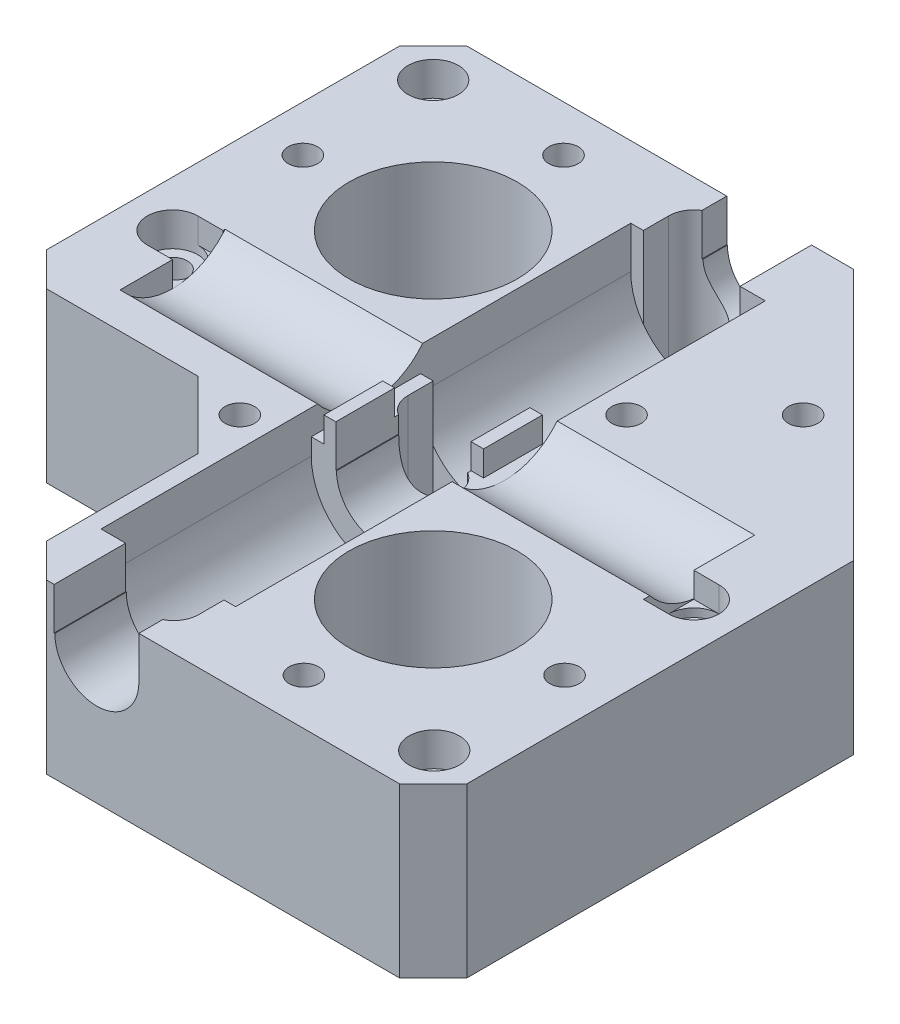
SolidWorks part; units mm, degrees
ref_plane "Front Plane" through (0, 0, 0) normal (0, 0, 1) x (1, 0, 0)
ref_plane "Top Plane" through (0, 0, 0) normal (0, 1, 0) x (1, 0, 0)
ref_plane "Right Plane" through (0, 0, 0) normal (1, 0, 0) x (0, 0, -1)
sketch "Sketch2" plane through (0, 0, 0) normal (0, 1, 0) x (1, 0, 0)
  line L1 (-40, -40) -> (40, -40)
  line L2 (-40, -40) -> (-40, 40)
  line L3 (-40, 40) -> (40, 40)
  line L4 (40, -40) -> (40, 40)
  line L5 (-40, -40) -> (40, 40) construction
  line L6 (-40, 40) -> (40, -40) construction
  point P0 (0, 0)
  dimension "D1" = 80
  dimension "D2" = 80
extrude "Boss-Extrude1" add sketch "Sketch2" along normal blind 20
sketch "Sketch4" plane through (0, 20, 0) normal (0, 1, 0) x (1, 0, 0)
  circle A0 centre (-3.5, 3.5) radius 1.75
  circle A1 centre (3.5, -3.5) radius 1.75
  circle A2 centre (-3.5, 34.5) radius 1.75
  circle A3 centre (-34.5, 34.5) radius 1.75
  circle A4 centre (-34.5, 3.5) radius 1.75
  circle A5 centre (3.6244, -34.5) radius 1.75
  circle A6 centre (34.6244, -34.5) radius 1.75
  circle A7 centre (34.5, -3.5) radius 1.75
  point P0 (3.5, -3.5)
  point P1 (-3.5, 3.5)
  point P2 (-3.5, 34.5)
  point P3 (-34.5, 3.5)
  point P4 (-34.5, 34.5)
  point P5 (34.5, -3.5)
  point P6 (3.6244, -34.5)
  point P7 (34.6244, -34.5)
  dimension "D16" = 3.5
  dimension "D17" = 3.5
  dimension "D18" = 3.5
  dimension "D19" = 3.5
  dimension "D20" = 3.5
  dimension "D21" = 3.5
  dimension "D22" = 3.5
  dimension "D23" = 3.5
  dimension "D1" = 3.5
  dimension "D2" = 3.5
  dimension "D3" = 3.5
  dimension "D4" = 3.5
  dimension "D5" = 31
  dimension "D6" = 31
  dimension "D7" = 0
  dimension "D8" = 0
  dimension "D9" = 31
  dimension "D10" = 31
  dimension "D11" = 31
  dimension "D12" = 31
  dimension "D13" = 31
  dimension "D14" = 31
  dimension "D15" = 0
extrude "Cut-Extrude1" cut sketch "Sketch4" against normal through all both and the other way through all
sketch "Sketch6" plane through (0, 20, 0) normal (0, 1, 0) x (1, 0, 0)
  line L4 (40, -40) -> (40, 40)
  line L5 (40, 40) -> (-40, 40)
  line L6 (-40, 40) -> (-40, -40)
  line L7 (-40, -40) -> (40, -40)
  line L8 (40, -40) -> (40, 40)
  line L9 (40, 40) -> (-40, 40)
  line L10 (-40, 40) -> (-40, -40)
  line L11 (-40, -40) -> (40, -40)
  circle A0 centre (3.6244, -34.5) radius 1.75 construction
  circle A1 centre (34.6244, -34.5) radius 1.75 construction
  circle A2 centre (34.5, -3.5) radius 1.75 construction
  circle A3 centre (3.5, -3.5) radius 1.75 construction
  circle A4 centre (-34.5, 3.5) radius 1.75 construction
  circle A5 centre (-3.5, 3.5) radius 1.75 construction
  circle A6 centre (-3.5, 34.5) radius 1.75 construction
  circle A7 centre (-34.5, 34.5) radius 1.75 construction
  circle A8 centre (3.6244, -34.5) radius 1.75
  circle A9 centre (34.6244, -34.5) radius 1.75
  circle A10 centre (34.5, -3.5) radius 1.75
  circle A11 centre (3.5, -3.5) radius 1.75
  circle A12 centre (-34.5, 3.5) radius 1.75
  circle A13 centre (-3.5, 3.5) radius 1.75
  circle A14 centre (-3.5, 34.5) radius 1.75
  circle A15 centre (-34.5, 34.5) radius 1.75
  circle A16 centre (-3.5, 3.5) radius 3
  circle A17 centre (3.5, -3.5) radius 3
  circle A18 centre (34.5, -3.5) radius 3
  circle A19 centre (34.6244, -34.5) radius 3
  circle A20 centre (3.6244, -34.5) radius 3
  circle A21 centre (-34.5, 3.5) radius 3
  circle A22 centre (-34.5, 34.5) radius 3
  circle A23 centre (-3.5, 34.5) radius 3
  circle M7 centre (-34.5, 34.5) radius 1.75
  dimension "D2" = 6
  dimension "D3" = 6
  dimension "D4" = 6
  dimension "D5" = 6
  dimension "D6" = 6
  dimension "D7" = 6
  dimension "D8" = 6
  dimension "D9" = 6
  dimension "D1" = 0
extrude "Cut-Extrude2" cut sketch "Sketch6" against normal blind 4 contours A22 M7 | M7 | A21 | A23 | A16 | A22 | A17 | A18 | A20 | A19 region at (-34.5, 20, -34.5) region at (-37.4151, 20, -34.5)
chamfer "Chamfer1" distance 4 angle 45 2 edges at (-40, 10, -40) (40, 10, 40)
sketch "Sketch7" plane through (0, 20, 0) normal (0, 1, 0) x (1, 0, 0)
  line L1 (-8, 6.5) -> (8, 6.5)
  line L2 (-8, 6.5) -> (-8, 31.5)
  line L3 (-8, 31.5) -> (8, 31.5)
  line L4 (8, 6.5) -> (8, 31.5)
  line L5 (-8, 6.5) -> (8, 31.5) construction
  line L6 (40, 40) -> (-36, 40)
  line L7 (-36, 40) -> (-40, 36)
  line L8 (-40, 36) -> (-40, -40)
  line L9 (-40, -40) -> (36, -40)
  line L10 (36, -40) -> (40, -36)
  line L11 (40, -36) -> (40, 40)
  line L12 (40, 40) -> (-36, 40)
  line L13 (-36, 40) -> (-40, 36)
  line L14 (-40, 36) -> (-40, -40)
  line L15 (-40, -40) -> (36, -40)
  line L16 (36, -40) -> (40, -36)
  line L17 (40, -36) -> (40, 40)
  line L18 (-8, 31.5) -> (8, 6.5) construction
  line L19 (-6.5, 3.5) -> (-0.5, 3.5)
  line L20 (-6.5, 3.5) -> (-6.5, 6.5)
  line L21 (-6.5, 6.5) -> (-0.5, 6.5)
  line L22 (-0.5, 3.5) -> (-0.5, 6.5)
  line L23 (-6.5, 34.5) -> (-0.5, 34.5)
  line L24 (-6.5, 34.5) -> (-6.5, 31.5)
  line L25 (-6.5, 31.5) -> (-0.5, 31.5)
  line L26 (-0.5, 34.5) -> (-0.5, 31.5)
  circle A0 centre (-3.5, 3.5) radius 3 construction
  circle A1 centre (-3.5, 34.5) radius 3 construction
  circle A2 centre (-3.5, 3.5) radius 3
  circle A3 centre (-3.5, 34.5) radius 3
  point P2 (0, 19)
  circle M12 centre (-3.5, 3.5) radius 3
  circle M13 centre (-3.5, 34.5) radius 3
  dimension "D2" = 16
  dimension "D3" = 0
  dimension "D4" = 25
  dimension "D5" = 19
  dimension "D1" = 0
extrude "Cut-Extrude5" cut sketch "Sketch7" against normal blind 4 contours L24 L3 M13 | L23 M13 | L26 L3 M13 | L1 L4 L3 L2 | L20 L1 M12 | L19 M12 | L22 L1 M12 region at (0, 20, -19) region at (-5.8299, 20, -5.8299) region at (-1.1701, 20, -5.8299) region at (-3.5, 20, -4.7732) region at (-5.8299, 20, -32.1701) region at (-1.1701, 20, -32.1701) region at (-3.5, 20, -33.2268)
sketch "Sketch8" plane through (0, 20, 0) normal (0, 1, 0) x (1, 0, 0)
  line L1 (-8, -31.5) -> (8, -31.5)
  line L2 (-8, -31.5) -> (-8, -6.5)
  line L3 (-8, -6.5) -> (8, -6.5)
  line L4 (8, -31.5) -> (8, -6.5)
  line L5 (-8, -31.5) -> (8, -6.5) construction
  line L6 (40, 40) -> (-36, 40)
  line L7 (-36, 40) -> (-40, 36)
  line L8 (-40, 36) -> (-40, -40)
  line L9 (-40, -40) -> (36, -40)
  line L10 (36, -40) -> (40, -36)
  line L11 (40, -36) -> (40, 40)
  line L12 (40, 40) -> (-36, 40)
  line L13 (-36, 40) -> (-40, 36)
  line L14 (-40, 36) -> (-40, -40)
  line L15 (-40, -40) -> (36, -40)
  line L16 (36, -40) -> (40, -36)
  line L17 (40, -36) -> (40, 40)
  line L18 (-8, -6.5) -> (8, -31.5) construction
  line L19 (6.6244, -34.5) -> (0.6244, -34.5)
  line L20 (6.6244, -34.5) -> (6.6244, -31.5)
  line L21 (6.6244, -31.5) -> (0.6244, -31.5)
  line L22 (0.6244, -34.5) -> (0.6244, -31.5)
  line L23 (0.5, -3.5) -> (6.5, -3.5)
  line L24 (0.5, -3.5) -> (0.5, -6.5)
  line L25 (0.5, -6.5) -> (6.5, -6.5)
  line L26 (6.5, -3.5) -> (6.5, -6.5)
  circle A0 centre (3.6244, -34.5) radius 3 construction
  circle A1 centre (3.5, -3.5) radius 3 construction
  circle A2 centre (3.6244, -34.5) radius 3
  circle A3 centre (3.5, -3.5) radius 3
  point P12 (0, -19)
  dimension "D2" = 25
  dimension "D3" = 19
  dimension "D4" = 16
  dimension "D1" = 0
extrude "Cut-Extrude6" cut sketch "Sketch8" against normal blind 4 contours L22 L23 | L23 L22 | L22 L24 L3 | L26 L22 L3 | L1 L4 L3 L2 | L19 L20 L1 | L19 | L22 L19 L1 | L19 region at (0, 20, 19) region at (1.2945, 20, 32.1701) region at (5.9543, 20, 32.1701) region at (3.6244, 20, 33.2268) region at (3.6244, 20, 35.7732) region at (1.1701, 20, 5.8299) region at (5.8299, 20, 5.8299) region at (3.5, 20, 4.7732) region at (3.5, 20, 2.2268)
sketch "Sketch9" plane through (0, 20, 0) normal (0, 1, 0) x (1, 0, 0)
  line L0 (6.6244, -31.5) -> (8, -31.5) construction
  line L1 (8, -31.5) -> (8, -6.5) construction
  line L2 (-8, -31.5) -> (-8, -6.5) construction
  line L3 (-8, -6.5) -> (0.5, -6.5) construction
  line L4 (-8, 6.5) -> (-6.5, 6.5) construction
  line L5 (-8, 6.5) -> (-8, 31.5) construction
  line L6 (40, 40) -> (-36, 40)
  line L7 (-36, 40) -> (-40, 36)
  line L8 (-40, 36) -> (-40, -40)
  line L9 (-40, -40) -> (36, -40)
  line L10 (36, -40) -> (40, -36)
  line L11 (40, -36) -> (40, 40)
  line L12 (40, 40) -> (-36, 40)
  line L13 (-36, 40) -> (-40, 36)
  line L14 (-40, 36) -> (-40, -40)
  line L15 (-40, -40) -> (36, -40)
  line L16 (36, -40) -> (40, -36)
  line L17 (40, -36) -> (40, 40)
  line L18 (-0.5, 31.5) -> (8, 31.5) construction
  line L19 (8, 6.5) -> (8, 31.5) construction
  line L20 (6.6244, -31.5) -> (8, -31.5)
  line L21 (8, -31.5) -> (8, -6.5)
  line L22 (-8, -31.5) -> (-8, -6.5)
  line L23 (-8, -6.5) -> (0.5, -6.5)
  line L24 (-8, 6.5) -> (-6.5, 6.5)
  line L25 (-8, 6.5) -> (-8, 31.5)
  line L26 (-0.5, 31.5) -> (8, 31.5)
  line L27 (8, 6.5) -> (8, 31.5)
  line L29 (-8, 6.5) -> (8, 6.5)
  line L30 (-8, 6.5) -> (-8, 31.5)
  line L31 (-8, 31.5) -> (8, 31.5)
  line L32 (8, 6.5) -> (8, 31.5)
  line L33 (-8, -31.5) -> (8, -31.5)
  line L34 (-8, -31.5) -> (-8, -6.5)
  line L35 (-8, -6.5) -> (8, -6.5)
  line L36 (8, -31.5) -> (8, -6.5)
  line M8 (-6.5, 6.5) -> (-8, 6.5)
  line M9 (-8, 6.5) -> (-8, 31.5)
  line M10 (-8, 31.5) -> (-6.5, 31.5)
  line M14 (-0.5, 31.5) -> (8, 31.5)
  line M15 (8, 31.5) -> (8, 6.5)
  line M16 (8, 6.5) -> (-0.5, 6.5)
  line M30 (0.6244, -31.5) -> (-8, -31.5)
  line M31 (-8, -31.5) -> (-8, -6.5)
  line M32 (-8, -6.5) -> (0.5, -6.5)
  line M36 (6.5, -6.5) -> (8, -6.5)
  line M37 (8, -6.5) -> (8, -31.5)
  line M38 (8, -31.5) -> (6.6244, -31.5)
  dimension "D1" = 0
extrude "Cut-Extrude7" cut sketch "Sketch9" against normal blind 13 contours L31 L29 M10 M9 M8 M16 M15 M14 | L35 L33 M32 M31 M30 M38 M37 M36 region at (0, 20, 19) region at (0, 20, -19)
fillet "Fillet1" radius 8 4 edges at (8, 7, -19) (-8, 7, -19) (8, 7, 19) (-8, 7, 19)
sketch "Sketch10" plane through (0, 20, 0) normal (0, 1, 0) x (1, 0, 0)
  line L0 (3.5, -0.5) -> (6.5, -0.5)
  line L1 (6.5, -8) -> (31.5, -8)
  line L2 (6.5, -8) -> (6.5, 8)
  line L3 (6.5, 8) -> (31.5, 8)
  line L4 (31.5, -8) -> (31.5, 8)
  line L5 (6.5, -8) -> (31.5, 8) construction
  line L6 (6.5, 8) -> (31.5, -8) construction
  line L8 (-31.5, -8) -> (-6.5, -8)
  line L9 (-31.5, -8) -> (-31.5, 8)
  line L10 (-31.5, 8) -> (-6.5, 8)
  line L11 (-6.5, -8) -> (-6.5, 8)
  line L12 (-31.5, -8) -> (-6.5, 8) construction
  line L13 (-31.5, 8) -> (-6.5, -8) construction
  line L14 (-34.5, 6.5) -> (-31.5, 6.5)
  line L15 (-34.5, 6.5) -> (-34.5, 0.5)
  line L16 (-34.5, 0.5) -> (-31.5, 0.5)
  line L17 (-31.5, 6.5) -> (-31.5, 0.5)
  line L18 (3.5, -0.5) -> (6.5, -0.5)
  line L19 (3.5, -0.5) -> (3.5, -6.5)
  line L20 (3.5, -6.5) -> (6.5, -6.5)
  line L21 (6.5, -0.5) -> (6.5, -6.5)
  line L22 (-3.5, 0.5) -> (-6.5, 0.5)
  line L23 (-3.5, 0.5) -> (-3.5, 6.5)
  line L24 (-3.5, 6.5) -> (-6.5, 6.5)
  line L25 (-6.5, 0.5) -> (-6.5, 6.5)
  line L26 (34.5, -0.5) -> (31.5, -0.5)
  line L27 (34.5, -0.5) -> (34.5, -6.5)
  line L28 (34.5, -6.5) -> (31.5, -6.5)
  line L29 (31.5, -0.5) -> (31.5, -6.5)
  arc A0 (6.5, -3.5) -> (0.5, -3.5) centre (3.5, -3.5) ccw construction
  arc A1 (6.5, -3.5) -> (0.5, -3.5) centre (3.5, -3.5) ccw
  circle A2 centre (-34.5, 3.5) radius 3 construction
  circle A3 centre (34.5, -3.5) radius 3
  circle A4 centre (34.5, -3.5) radius 3
  arc A5 (-6.5, 3.5) -> (-0.5, 3.5) centre (-3.5, 3.5) ccw construction
  circle A6 centre (-34.5, 3.5) radius 3
  arc A7 (-6.5, 3.5) -> (-0.5, 3.5) centre (-3.5, 3.5) ccw
  point P0 (19, 0)
  point P20 (-19, 0)
  line M15 (-6.5, 3.5) -> (-6.5, 6.5)
  line M16 (-6.5, 6.5) -> (-8, 6.5)
  line M17 (-8, 6.5) -> (-8, 31.5)
  line M23 (8, 31.5) -> (8, 6.5)
  line M24 (8, 6.5) -> (-0.5, 6.5)
  arc M26 (-0.5, 3.5) -> (-6.5, 3.5) centre (-3.5, 3.5) cw
  circle M27 centre (-34.5, 3.5) radius 3
  circle M29 centre (34.5, -3.5) radius 3
  line M39 (-8, -31.5) -> (-8, -6.5)
  line M40 (-8, -6.5) -> (0.5, -6.5)
  arc M42 (0.5, -3.5) -> (6.5, -3.5) centre (3.5, -3.5) cw
  line M43 (6.5, -3.5) -> (6.5, -6.5)
  line M44 (6.5, -6.5) -> (8, -6.5)
  line M45 (8, -6.5) -> (8, -31.5)
  dimension "D5" = 0
  dimension "D1" = 16
  dimension "D2" = 25
  dimension "D3" = 19
  dimension "D4" = 0
  dimension "D6" = 25
  dimension "D7" = 19
  dimension "D8" = 16
  dimension "D9" = 0
extrude "Cut-Extrude8" cut sketch "Sketch10" against normal blind 3 contours L27 M29 | L26 L4 M29 | L27 M29 | L28 L4 M29 | L1 L4 L3 L2 M23 M24 M43 M44 M45 | L19 L20 M43 M42 | L2 L0 M42 | L11 L10 L9 L8 M40 M15 M16 M17 M39 | L23 L24 M15 M26 | L22 L11 M26 | L16 L9 M27 | L15 M27 | L14 L9 M27 region at (4.9002, 20, 3.78) region at (5.8299, 20, 1.1701) region at (19.1337, 20, 0) region at (32.1701, 20, 1.1701) region at (32.1701, 20, 5.8299) region at (33.2268, 20, 3.5) region at (35.7732, 20, 3.5) region at (-19.1337, 20, 0) region at (-32.1701, 20, -1.1701) region at (-32.1701, 20, -5.8299) region at (-33.2268, 20, -3.5) region at (-5.8299, 20, -1.1701) region at (-4.9002, 20, -3.78)
sketch "Sketch12" plane through (-31.5, 0, 0) normal (1, 0, 0) x (0, 0, -1)
  line L0 (0.5, 17) -> (8, 17)
  line L1 (8, 20) -> (8, 17)
  line L4 (0.5, 20) -> (-8, 20)
  line L5 (-8, 20) -> (-8, 17)
  line L6 (-8, 17) -> (0.5, 17)
  line L7 (0.5, 17) -> (0.5, 20)
  line L8 (0.5, 20) -> (-8, 20)
  line L9 (-8, 20) -> (-8, 17)
  line L10 (-8, 17) -> (0.5, 17)
  line L11 (0.5, 17) -> (0.5, 20)
  line L12 (8, 20) -> (6.5, 20)
  line L13 (6.5, 20) -> (6.5, 17)
  line L14 (6.5, 17) -> (8, 17)
  line L15 (8, 17) -> (8, 20)
  line L16 (8, 20) -> (6.5, 20)
  line L17 (6.5, 20) -> (6.5, 17)
  line L18 (6.5, 17) -> (8, 17)
  line L19 (8, 17) -> (8, 20)
  circle A0 centre (0.5, 25) radius 8
  line M10 (-8, 20) -> (-8, 17)
  line M11 (-8, 17) -> (0.5, 17)
  dimension "D3" = 16
  dimension "D4" = 8
  dimension "D1" = 0
  dimension "D2" = 0
extrude "Boss-Extrude3" add sketch "Sketch12" along normal blind 23.5 contours A0 L0 L17 | A0 L17 L0 L1 L16 | A0 L8 M10 M11 region at (-31.5, 17.782, -5.0555) region at (-31.5, 18.2083, 5.6741) region at (-31.5, 18.4886, -7.2554)
mirror "Mirror1" about plane through (0, 0, 0) normal (1, 0, 0) of "Boss-Extrude3"
sketch "Sketch13" plane through (0, 0, 6.5) normal (0, 0, 1) x (1, 0, 0)
  line L9 (8, 15) -> (8, 17)
  line L10 (8, 17) -> (6.5, 17)
  line L11 (6.5, 17) -> (6.5, 16)
  line L12 (6.5, 16) -> (0.5, 16)
  line L13 (0.5, 16) -> (0.5, 20)
  line L14 (0.5, 20) -> (-6.5, 20)
  line L15 (-6.5, 20) -> (-6.5, 17)
  line L16 (-6.5, 17) -> (-8, 17)
  line L17 (-8, 17) -> (-8, 15)
  line L18 (8, 15) -> (8, 17)
  line L19 (8, 17) -> (6.5, 17)
  line L20 (6.5, 17) -> (6.5, 16)
  line L21 (6.5, 16) -> (0.5, 16)
  line L22 (0.5, 16) -> (0.5, 20)
  line L23 (0.5, 20) -> (-6.5, 20)
  line L24 (-6.5, 20) -> (-6.5, 17)
  line L25 (-6.5, 17) -> (-8, 17)
  line L26 (-8, 17) -> (-8, 15)
  circle A0 centre (0, 15) radius 4
  arc A2 (-8, 15) -> (0, 7) centre (0, 15) ccw
  arc A3 (0, 7) -> (8, 15) centre (0, 15) ccw
  arc A4 (-8, 15) -> (0, 7) centre (0, 15) ccw
  arc A5 (0, 7) -> (8, 15) centre (0, 15) ccw
  dimension "D2" = 8
  dimension "D1" = 0
extrude "Cut-Extrude9" cut sketch "Sketch13" against normal through all both and the other way through all contours A0
sketch "Sketch14" plane through (0, 16, 0) normal (0, 1, 0) x (1, 0, 0)
  line L0 (-3.873, 36.2098) -> (-3.873, 37.4767) construction
  line L1 (-6.5, 6.5) -> (-0.5, 6.5)
  line L2 (-6.5, 6.5) -> (-6.5, 3.5)
  line L3 (-6.5, 3.5) -> (-0.5, 3.5)
  line L4 (-0.5, 6.5) -> (-0.5, 3.5)
  line L5 (0.5, -6.5) -> (6.5, -6.5)
  line L6 (0.5, -6.5) -> (0.5, -3.5)
  line L7 (0.5, -3.5) -> (6.5, -3.5)
  line L8 (6.5, -6.5) -> (6.5, -3.5)
  line L9 (-6.5, 34.5) -> (-6.5, 31.5) construction
  line L10 (-6.5, 31.5) -> (-3.873, 31.5) construction
  line L11 (-3.873, 31.5) -> (-3.873, 32.7902) construction
  line L12 (3.873, -36.2323) -> (3.873, -37.4897) construction
  line L13 (6.6244, -34.5) -> (6.6244, -31.5) construction
  line L14 (6.6244, -31.5) -> (3.873, -31.5) construction
  line L15 (3.873, -31.5) -> (3.873, -32.7677) construction
  line L16 (-3.873, 36.2098) -> (-3.873, 37.4767)
  line L17 (-6.5, 34.5) -> (-6.5, 31.5)
  line L18 (-6.5, 31.5) -> (-3.873, 31.5)
  line L19 (-3.873, 31.5) -> (-3.873, 32.7902)
  line L20 (3.873, -36.2323) -> (3.873, -37.4897)
  line L21 (6.6244, -34.5) -> (6.6244, -31.5)
  line L22 (6.6244, -31.5) -> (3.873, -31.5)
  line L23 (3.873, -31.5) -> (3.873, -32.7677)
  line L25 (-6.5, 34.5) -> (-0.5, 34.5)
  line L26 (-6.5, 34.5) -> (-6.5, 31.5)
  line L27 (-6.5, 31.5) -> (-0.5, 31.5)
  line L28 (-0.5, 34.5) -> (-0.5, 31.5)
  line L29 (0.6244, -34.5) -> (6.6244, -34.5)
  line L30 (0.6244, -34.5) -> (0.6244, -31.5)
  line L31 (0.6244, -31.5) -> (6.6244, -31.5)
  line L32 (6.6244, -34.5) -> (6.6244, -31.5)
  arc A0 (-3.873, 5.2098) -> (-3.873, 1.7902) centre (-3.5, 3.5) ccw construction
  arc A1 (3.873, -5.2098) -> (3.873, -1.7902) centre (3.5, -3.5) ccw construction
  arc A2 (-3.873, 5.2098) -> (-3.873, 1.7902) centre (-3.5, 3.5) ccw
  arc A3 (3.873, -5.2098) -> (3.873, -1.7902) centre (3.5, -3.5) ccw
  circle A4 centre (3.5, -3.5) radius 3
  circle A5 centre (-3.5, 3.5) radius 3
  arc A6 (-3.873, 37.4767) -> (-6.5, 34.5) centre (-3.5, 34.5) ccw construction
  arc A7 (-3.873, 36.2098) -> (-3.873, 32.7902) centre (-3.5, 34.5) ccw construction
  arc A8 (3.873, -37.4897) -> (6.6244, -34.5) centre (3.6244, -34.5) ccw construction
  arc A9 (3.873, -36.2323) -> (3.873, -32.7677) centre (3.6244, -34.5) ccw construction
  arc A10 (-0.5, 34.5) -> (-6.5, 34.5) centre (-3.5, 34.5) ccw construction
  arc A11 (0.6244, -34.5) -> (3.873, -37.4897) centre (3.6244, -34.5) ccw construction
  arc A12 (-3.873, 37.4767) -> (-6.5, 34.5) centre (-3.5, 34.5) ccw
  arc A13 (-3.873, 36.2098) -> (-3.873, 32.7902) centre (-3.5, 34.5) ccw
  arc A14 (3.873, -37.4897) -> (6.6244, -34.5) centre (3.6244, -34.5) ccw
  arc A15 (3.873, -36.2323) -> (3.873, -32.7677) centre (3.6244, -34.5) ccw
  arc A16 (-0.5, 34.5) -> (-6.5, 34.5) centre (-3.5, 34.5) ccw
  arc A17 (0.6244, -34.5) -> (3.873, -37.4897) centre (3.6244, -34.5) ccw
  circle A18 centre (3.6244, -34.5) radius 3
  circle A19 centre (-3.5, 34.5) radius 3
  point P29 (0, 0)
extrude "Cut-Extrude14" cut sketch "Sketch14" against normal blind 12 contours A4 | L5 L8 L7 L6 | A5 | L1 L4 L3 L2
sketch "Sketch16" plane through (0, 20, 0) normal (0, 1, 0) x (1, 0, 0)
  line L0 (6.6244, -34.5) -> (6.6244, -31.5) construction
  line L1 (-6.5, 34.5) -> (-6.5, 31.5) construction
  line L2 (6.6244, -34.5) -> (6.6244, -31.5)
  line L3 (-6.5, 34.5) -> (-6.5, 31.5)
  line L5 (-6.5, 34.5) -> (-0.5, 34.5)
  line L6 (-6.5, 34.5) -> (-6.5, 31.5)
  line L7 (-6.5, 31.5) -> (-0.5, 31.5)
  line L8 (-0.5, 34.5) -> (-0.5, 31.5)
  line L9 (6.6244, -31.5) -> (0.6244, -31.5)
  line L10 (6.6244, -31.5) -> (6.6244, -34.5)
  line L11 (6.6244, -34.5) -> (0.6244, -34.5)
  line L12 (0.6244, -31.5) -> (0.6244, -34.5)
  arc A0 (0.6244, -34.5) -> (6.6244, -34.5) centre (3.6244, -34.5) ccw construction
  arc A1 (-0.5, 34.5) -> (-6.5, 34.5) centre (-3.5, 34.5) ccw construction
  arc A2 (0.6244, -34.5) -> (6.6244, -34.5) centre (3.6244, -34.5) ccw
  arc A3 (-0.5, 34.5) -> (-6.5, 34.5) centre (-3.5, 34.5) ccw
  circle A4 centre (3.6244, -34.5) radius 3
  circle A5 centre (-3.5, 34.5) radius 3
  line M6 (6.6244, -31.5) -> (6.6244, -34.5)
  arc M7 (6.6244, -34.5) -> (0.6244, -34.5) centre (3.6244, -34.5) cw
  line M8 (0.6244, -34.5) -> (0.6244, -31.5)
  line M20 (-6.5, 31.5) -> (-6.5, 34.5)
  arc M21 (-6.5, 34.5) -> (-0.5, 34.5) centre (-3.5, 34.5) cw
  line M22 (-0.5, 34.5) -> (-0.5, 31.5)
extrude "Cut-Extrude15" cut sketch "Sketch16" against normal blind 16 contours L11 M7 | L11 A4 | A4 L9 M6 | A4 L9 M8 | A5 L7 M22 | A5 L5 | A5 L7 M20 | L5 M21 region at (5.9543, 20, 32.1701) region at (3.6244, 20, 35.7732) region at (3.6244, 20, 33.2268) region at (1.2945, 20, 32.1701) region at (-5.8299, 20, -32.1701) region at (-3.5, 20, -35.7732) region at (-3.5, 20, -33.2268) region at (-1.1701, 20, -32.1701)
sketch "Sketch17" plane through (0, 0, 40) normal (0, 0, 1) x (1, 0, 0)
  line L1 (-5.0821, 20) -> (5, 20)
  line L2 (-5.0821, 20) -> (-5.0821, 15)
  line L3 (-5.0821, 15) -> (5, 15)
  line L4 (-40, 0) -> (36, 0)
  line L5 (36, 0) -> (36, 20)
  line L6 (36, 20) -> (-40, 20)
  line L7 (-40, 20) -> (-40, 0)
  line L8 (-40, 0) -> (36, 0)
  line L9 (36, 0) -> (36, 20)
  line L10 (36, 20) -> (-40, 20)
  line L11 (-40, 20) -> (-40, 0)
  line L12 (5, 20) -> (5, 15)
  circle A0 centre (0, 15) radius 4 construction
  circle A1 centre (0, 15) radius 4
  circle A2 centre (0, 15) radius 5
  circle M5 centre (0, 15) radius 4
  line M8 (36, 20) -> (-40, 20)
  dimension "D1" = 0
extrude "Cut-Extrude16" cut sketch "Sketch17" against normal through all contours A2 L12 M8 | L3 A2 M5 | L3 M5 | L3 M5 | A2 L10 L2 L3 | L3 A2 M5 | A1 | A2 region at (-3.9655, 18.7848, 40) region at (3.8832, 18.8832, 40) region at (3.4565, 18.4565, 40) region at (0, 10.1118, 40) region at (0, 13.3023, 40) region at (0, 16.6977, 40)
sketch "Sketch18" plane through (0, 20, 0) normal (0, 1, 0) x (1, 0, 0)
  line L1 (-40, -40) -> (-10, -40)
  line L2 (-40, -40) -> (-40, -10)
  line L3 (-40, -10) -> (-10, -10)
  line L4 (-10, -40) -> (-10, -10)
  line L17 (-40, -40) -> (-5.0821, -40)
  line L18 (-5.0821, -40) -> (-5.0821, -31.5)
  line L19 (-5.0821, -31.5) -> (-8, -31.5)
  line L20 (-8, -31.5) -> (-8, -5.745)
  line L21 (-8, -5.745) -> (-31.5, -5.745)
  line L22 (-31.5, -5.745) -> (-31.5, 0.5)
  line L23 (-31.5, 0.5) -> (-34.5, 0.5)
  line L24 (-34.5, 6.5) -> (-31.5, 6.5)
  line L25 (-31.5, 6.5) -> (-31.5, 6.745)
  line L26 (-31.5, 6.745) -> (-8, 6.745)
  line L27 (-8, 6.745) -> (-8, 31.5)
  line L28 (-8, 31.5) -> (-6.5, 31.5)
  line L29 (-6.5, 31.5) -> (-6.5, 34.5)
  line L30 (-5.0821, 37.0489) -> (-5.0821, 40)
  line L31 (-5.0821, 40) -> (-36, 40)
  line L32 (-36, 40) -> (-40, 36)
  line L33 (-40, 36) -> (-40, -40)
  line L34 (-40, -40) -> (-5.0821, -40)
  line L35 (-5.0821, -40) -> (-5.0821, -31.5)
  line L36 (-5.0821, -31.5) -> (-8, -31.5)
  line L37 (-8, -31.5) -> (-8, -5.745)
  line L38 (-8, -5.745) -> (-31.5, -5.745)
  line L39 (-31.5, -5.745) -> (-31.5, 0.5)
  line L40 (-31.5, 0.5) -> (-34.5, 0.5)
  line L41 (-34.5, 6.5) -> (-31.5, 6.5)
  line L42 (-31.5, 6.5) -> (-31.5, 6.745)
  line L43 (-31.5, 6.745) -> (-8, 6.745)
  line L44 (-8, 6.745) -> (-8, 31.5)
  line L45 (-8, 31.5) -> (-6.5, 31.5)
  line L46 (-6.5, 31.5) -> (-6.5, 34.5)
  line L47 (-5.0821, 37.0489) -> (-5.0821, 40)
  line L48 (-5.0821, 40) -> (-36, 40)
  line L49 (-36, 40) -> (-40, 36)
  line L50 (-40, 36) -> (-40, -40)
  arc A2 (-34.5, 6.5) -> (-34.5, 0.5) centre (-34.5, 3.5) ccw
  arc A3 (-5.0821, 37.0489) -> (-6.5, 34.5) centre (-3.5, 34.5) ccw
  arc A4 (-34.5, 6.5) -> (-34.5, 0.5) centre (-34.5, 3.5) ccw
  arc A5 (-5.0821, 37.0489) -> (-6.5, 34.5) centre (-3.5, 34.5) ccw
  line M24 (-40, -40) -> (-5.0821, -40)
  line M42 (-40, 36) -> (-40, -40)
  dimension "D2" = 30
  dimension "D3" = 30
  dimension "D1" = 0
extrude "Cut-Extrude17" cut sketch "Sketch18" against normal through all both and the other way through all contours L4 L3 M24 M42 region at (-25, 20, 25)
chamfer "Chamfer2" distance 4 angle 45 2 edges at (-40, 10, 10) (-10, 10, 40)
chamfer "Chamfer3" distance 30 angle 45 1 edges at (40, 10, -40)
sketch "Sketch21" plane through (0, 0, 0) normal (0, -1, 0) x (1, 0, 0)
  line L11 (-36, -40) -> (10, -40)
  line L12 (10, -40) -> (40, -10)
  line L13 (40, -10) -> (40, 36)
  line L14 (40, 36) -> (36, 40)
  line L15 (36, 40) -> (-6, 40)
  line L16 (-6, 40) -> (-10, 36)
  line L17 (-10, 36) -> (-10, 10)
  line L18 (-10, 10) -> (-36, 10)
  line L19 (-36, 10) -> (-40, 6)
  line L20 (-40, 6) -> (-40, -36)
  line L21 (-40, -36) -> (-36, -40)
  line L22 (-36, -40) -> (10, -40)
  line L23 (10, -40) -> (40, -10)
  line L24 (40, -10) -> (40, 36)
  line L25 (40, 36) -> (36, 40)
  line L26 (36, 40) -> (-6, 40)
  line L27 (-6, 40) -> (-10, 36)
  line L28 (-10, 36) -> (-10, 10)
  line L29 (-10, 10) -> (-36, 10)
  line L30 (-36, 10) -> (-40, 6)
  line L31 (-40, 6) -> (-40, -36)
  line L32 (-40, -36) -> (-36, -40)
  circle A0 centre (3.5, 3.5) radius 1.75 construction
  circle A1 centre (3.5, 3.5) radius 1.75
  circle A2 centre (-3.5, -3.5) radius 1.75 construction
  circle A3 centre (-3.5, -3.5) radius 1.75
  circle A4 centre (-19, -19) radius 10
  circle A5 centre (19, 19) radius 10
  dimension "D2" = 20
  dimension "D3" = 20
  dimension "D4" = 15.5
  dimension "D5" = 15.5
  dimension "D6" = 15.5
  dimension "D7" = 15.5
  dimension "D1" = 0
extrude "Cut-Extrude20" cut sketch "Sketch21" against normal through all both and the other way through all contours A4 | A5
sketch "Sketch22" plane through (0, 0, 0) normal (0, -1, 0) x (1, 0, 0)
  circle A0 centre (19, 19) radius 10 construction
  circle A1 centre (-19, -19) radius 10 construction
  circle A2 centre (19, 19) radius 10
  circle A3 centre (-19, -19) radius 10
  circle A4 centre (-19, -19) radius 11
  circle A5 centre (19, 19) radius 11
  dimension "D1" = 22
  dimension "D2" = 22
extrude "Cut-Extrude21" cut sketch "Sketch22" against normal blind 3
chamfer "Chamfer4" distance 8 angle 45 1 edges at (-10, 10, 10)
sketch "Sketch23" plane through (0, 0, 0) normal (0, -1, 0) x (1, 0, 0)
  line L12 (-36, -40) -> (10, -40)
  line L13 (10, -40) -> (40, -10)
  line L14 (40, -10) -> (40, 36)
  line L15 (40, 36) -> (36, 40)
  line L16 (36, 40) -> (-6, 40)
  line L17 (-6, 40) -> (-10, 36)
  line L18 (-10, 36) -> (-10, 18)
  line L19 (-10, 18) -> (-18, 10)
  line L20 (-18, 10) -> (-36, 10)
  line L21 (-36, 10) -> (-40, 6)
  line L22 (-40, 6) -> (-40, -36)
  line L23 (-40, -36) -> (-36, -40)
  line L24 (-36, -40) -> (10, -40)
  line L25 (10, -40) -> (40, -10)
  line L26 (40, -10) -> (40, 36)
  line L27 (40, 36) -> (36, 40)
  line L28 (36, 40) -> (-6, 40)
  line L29 (-6, 40) -> (-10, 36)
  line L30 (-10, 36) -> (-10, 18)
  line L31 (-10, 18) -> (-18, 10)
  line L32 (-18, 10) -> (-36, 10)
  line L33 (-36, 10) -> (-40, 6)
  line L34 (-40, 6) -> (-40, -36)
  line L35 (-40, -36) -> (-36, -40)
  circle A0 centre (-34.5, -19) radius 1.75
  circle A1 centre (-19, -34.5) radius 1.75
  circle A2 centre (-34.5, -34.5) radius 3 construction
  circle A3 centre (-34.5, -34.5) radius 3
  circle A4 centre (-11.5, 11.5) radius 1.75
  circle A5 centre (11.5, -11.5) radius 1.75
  circle A6 centre (19.1244, 34.5) radius 1.75
  circle A7 centre (34.6244, 34.5) radius 3
  circle A8 centre (34.6244, 34.5) radius 3
  circle A9 centre (34.6244, 19) radius 1.75
  circle A10 centre (22, -22) radius 1.75
  dimension "D2" = 3.5
  dimension "D3" = 3.5
  dimension "D8" = 3.5
  dimension "D11" = 3.5
  dimension "D17" = 3.5
  dimension "D18" = 3.5
  dimension "D19" = 3.5
  dimension "D4" = 0
  dimension "D5" = 0
  dimension "D6" = 15.5
  dimension "D7" = 15.5
  dimension "D9" = 6.5
  dimension "D10" = 6.5
  dimension "D12" = 11.5
  dimension "D13" = 11.5
  dimension "D14" = 0
  dimension "D15" = 15.5
  dimension "D16" = 15.5
  dimension "D20" = 22
  dimension "D21" = 22
  dimension "D1" = 0
extrude "Cut-Extrude22" cut sketch "Sketch23" against normal through all both and the other way through all contours A1 | A10 | A5 | A9 | A6 | A4 | A0
sketch "Sketch25" plane through (0, 0, 0) normal (0, -1, 0) x (1, 0, 0)
  line L1 (11.5, -8.3246) -> (8.75, -9.9123)
  line L2 (8.75, -9.9123) -> (8.75, -13.0877)
  line L3 (8.75, -13.0877) -> (11.5, -14.6754)
  line L4 (11.5, -14.6754) -> (14.25, -13.0877)
  line L5 (14.25, -13.0877) -> (14.25, -9.9123)
  line L6 (14.25, -9.9123) -> (11.5, -8.3246)
  line L7 (-11.5, 14.6754) -> (-14.25, 13.0877)
  line L8 (-14.25, 13.0877) -> (-14.25, 9.9123)
  line L9 (-14.25, 9.9123) -> (-11.5, 8.3246)
  line L10 (-11.5, 8.3246) -> (-8.75, 9.9123)
  line L11 (-8.75, 9.9123) -> (-8.75, 13.0877)
  line L12 (-8.75, 13.0877) -> (-11.5, 14.6754)
  line L13 (-34.5, -15.8246) -> (-37.25, -17.4123)
  line L14 (-37.25, -17.4123) -> (-37.25, -20.5877)
  line L15 (-37.25, -20.5877) -> (-34.5, -22.1754)
  line L16 (-34.5, -22.1754) -> (-31.75, -20.5877)
  line L17 (-31.75, -20.5877) -> (-31.75, -17.4123)
  line L18 (-31.75, -17.4123) -> (-34.5, -15.8246)
  line L19 (-22.1754, -34.5) -> (-20.5877, -37.25)
  line L20 (-20.5877, -37.25) -> (-17.4123, -37.25)
  line L21 (-17.4123, -37.25) -> (-15.8246, -34.5)
  line L22 (-15.8246, -34.5) -> (-17.4123, -31.75)
  line L23 (-17.4123, -31.75) -> (-20.5877, -31.75)
  line L24 (-20.5877, -31.75) -> (-22.1754, -34.5)
  line L25 (25.1754, -22) -> (23.5877, -19.25)
  line L26 (23.5877, -19.25) -> (20.4123, -19.25)
  line L27 (20.4123, -19.25) -> (18.8246, -22)
  line L28 (18.8246, -22) -> (20.4123, -24.75)
  line L29 (20.4123, -24.75) -> (23.5877, -24.75)
  line L30 (23.5877, -24.75) -> (25.1754, -22)
  line L31 (34.6244, 22.1754) -> (31.8744, 20.5877)
  line L32 (31.8744, 20.5877) -> (31.8744, 17.4123)
  line L33 (31.8744, 17.4123) -> (34.6244, 15.8246)
  line L34 (34.6244, 15.8246) -> (37.3744, 17.4123)
  line L35 (37.3744, 17.4123) -> (37.3744, 20.5877)
  line L36 (37.3744, 20.5877) -> (34.6244, 22.1754)
  line L37 (22.2998, 34.5) -> (20.7121, 37.25)
  line L38 (20.7121, 37.25) -> (17.5367, 37.25)
  line L39 (17.5367, 37.25) -> (15.949, 34.5)
  line L40 (15.949, 34.5) -> (17.5367, 31.75)
  line L41 (17.5367, 31.75) -> (20.7121, 31.75)
  line L42 (20.7121, 31.75) -> (22.2998, 34.5)
  circle A0 centre (-19, -34.5) radius 1.75 construction
  circle A1 centre (-34.5, -19) radius 1.75 construction
  circle A2 centre (19.1244, 34.5) radius 1.75 construction
  circle A3 centre (34.6244, 19) radius 1.75 construction
  circle A4 centre (22, -22) radius 1.75 construction
  circle A5 centre (11.5, -11.5) radius 1.75 construction
  circle A6 centre (-11.5, 11.5) radius 1.75 construction
  circle A7 centre (-19, -34.5) radius 1.75
  circle A8 centre (-34.5, -19) radius 1.75
  circle A9 centre (19.1244, 34.5) radius 1.75
  circle A10 centre (34.6244, 19) radius 1.75
  circle A11 centre (22, -22) radius 1.75
  circle A12 centre (11.5, -11.5) radius 1.75
  circle A13 centre (-11.5, 11.5) radius 1.75
  circle A14 centre (11.5, -11.5) radius 2.75 construction
  circle A15 centre (-11.5, 11.5) radius 2.75 construction
  circle A16 centre (-34.5, -19) radius 2.75 construction
  circle A17 centre (-19, -34.5) radius 2.75 construction
  circle A18 centre (22, -22) radius 2.75 construction
  circle A19 centre (34.6244, 19) radius 2.75 construction
  circle A20 centre (19.1244, 34.5) radius 2.75 construction
  dimension "D1" = 5.5
  dimension "D2" = 5.5
  dimension "D3" = 5.5
  dimension "D4" = 5.5
  dimension "D5" = 5.5
  dimension "D6" = 5.5
  dimension "D7" = 5.5
extrude "Cut-Extrude23" cut sketch "Sketch25" against normal blind 16
